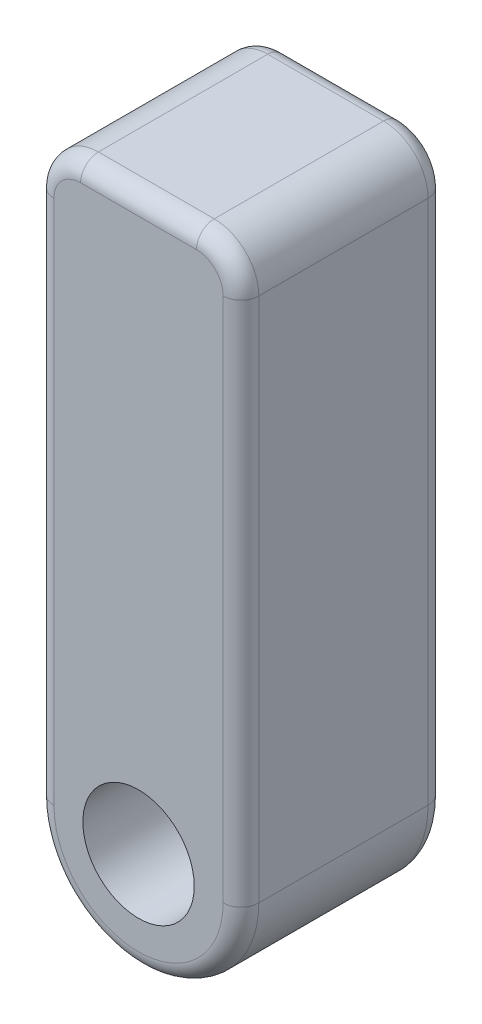
SolidWorks part; units mm, degrees
ref_plane "Front Plane" through (0, 0, 0) normal (0, 0, 1) x (1, 0, 0)
ref_plane "Top Plane" through (0, 0, 0) normal (0, 1, 0) x (1, 0, 0)
ref_plane "Right Plane" through (0, 0, 0) normal (1, 0, 0) x (0, 0, -1)
sketch "Sketch1" plane through (0, 0, 0) normal (0, 0, 1) x (1, 0, 0)
  line L0 (0, -64) -> (0, 64) construction
  line L1 (-11.5, -12.5) -> (11.5, -12.5)
  line L2 (-11.5, -12.5) -> (-11.5, 64)
  line L3 (-11.5, 64) -> (11.5, 64)
  line L4 (11.5, -12.5) -> (11.5, 64)
  line L5 (-11.5, -12.5) -> (11.5, 64) construction
  line L6 (-11.5, 64) -> (11.5, -12.5) construction
  line L7 (-5.2, 41) -> (5.2, 41)
  line L8 (-5.2, 41) -> (-5.2, 56.4)
  line L9 (-5.2, 56.4) -> (5.2, 56.4)
  line L10 (5.2, 41) -> (5.2, 56.4)
  line L11 (-5.2, 41) -> (5.2, 56.4) construction
  line L12 (-5.2, 56.4) -> (5.2, 41) construction
  circle A0 centre (0, 0) radius 6.25
  circle A1 centre (0, 0) radius 11.5
  point P3 (0, 25.75)
  point P8 (0, 48.7)
  point P15 (0, 0)
  dimension "D1" = 12.5
  dimension "D2" = 23
  dimension "D3" = 41
  dimension "D4" = 23
  dimension "D5" = 10.4
  dimension "D6" = 6.3
  dimension "D7" = 15.4
  dimension "D8" = 12.5
  dimension "D9" = 7.6
extrude "Boss-Extrude1" add sketch "Sketch1" along normal blind 23 contours A1 L4 L3 L2 L10 L7 L8 L9 | A1 A0 region at (0, 34.68, 0) region at (0, 11.1747, 0)
chamfer "Chamfer2" distance 1 angle 70 4 edges at (5.2, 48.7, 0) (0, 41, 0) (-5.2, 48.7, 0) (0, 56.4, 0) first distance on face at (0, 29.125, 0)
fillet "Fillet2" radius 5 2 edges at (-11.5, 64, 11.5) (11.5, 64, 11.5)
fillet "Fillet3" radius 2 12 edges at (0, -11.5, 0) (11.5, 29.5, 0) (10.0355, 62.5355, 0) (0, 64, 0) (-10.0355, 62.5355, 0) (0, -11.5, 23) (11.5, 29.5, 23) (10.0355, 62.5355, 23) (0, 64, 23) (-10.0355, 62.5355, 23) (-11.5, 29.5, 0) (-11.5, 29.5, 23)
sketch "Sketch2" plane through (0, 0, 23) normal (0, 0, 1) x (1, 0, 0)
  line L4 (-5.2, 41) -> (5.2, 41)
  line L5 (-5.2, 41) -> (-5.2, 56.4)
  line L6 (-5.2, 56.4) -> (5.2, 56.4)
  line L7 (5.2, 41) -> (5.2, 56.4)
extrude "Boss-Extrude2" add sketch "Sketch2" against normal blind 1
